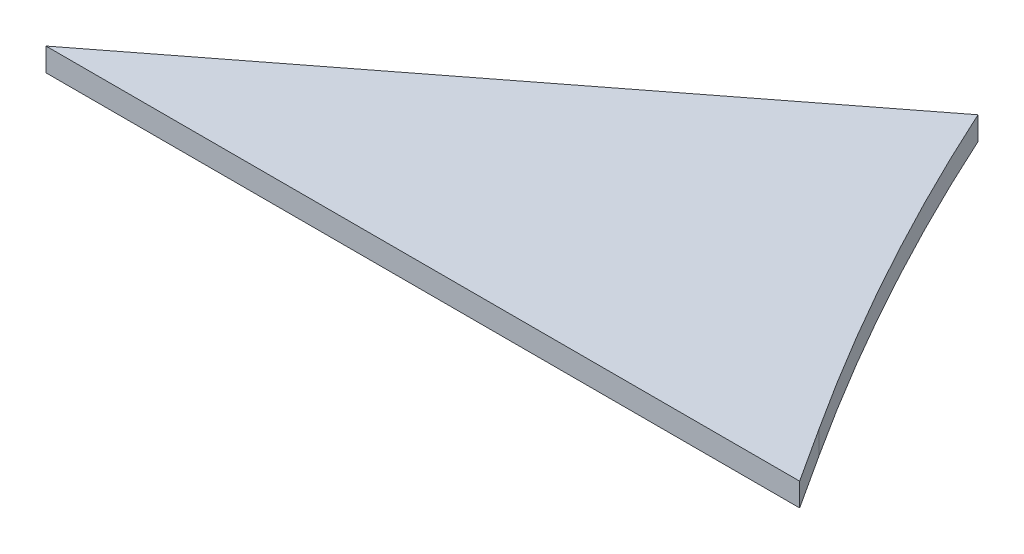
SolidWorks part; units mm, degrees
material "AISI 4130 Steel, normalized at 870C"
ref_plane "Front Plane" through (0, 0, 0) normal (0, 0, 1) x (1, 0, 0)
ref_plane "Top Plane" through (0, 0, 0) normal (0, 1, 0) x (1, 0, 0)
ref_plane "Right Plane" through (0, 0, 0) normal (1, 0, 0) x (0, 0, -1)
sketch "Sketch1" plane through (0, 0, 0) normal (0, 1, 0) x (1, 0, 0)
  line L0 (0, 0) -> (-57.4701, -44.45)
  line L1 (-57.4701, -44.45) -> (24.9464, -44.45)
  line L2 (24.9464, -44.45) -> (21.0374, -38.4076)
  line L3 (0, 0) -> (0, -44.45) construction
  arc A0 (21.0374, -38.4076) -> (0, 0) centre (272.7305, 124.42) cw
  dimension "D2" = 299.7704
  dimension "D3" = 43.7917
  dimension "D1" = 37.72
  dimension "D4" = 57.1
  dimension "D5" = 44.45
base flange "Base-Flange1" sketch "Sketch1" thickness 2.54 reverse thickness direction no parameters "D1"=0.7366
sketch "Bend-Lines1" [suppressed] plane through (0, 0, 0) normal (0, 1, 0) x (1, 0, 0)
sketch "Bounding-Box1" [suppressed] plane through (0, 0, 0) normal (0, 1, 0) x (1, 0, 0)
sheet metal parameters "Sheet-Metal1" thickness 2.54 parameters "D1"=0.7366
flat pattern "Flat-Pattern1" [suppressed]
sketch "Bend-Lines2" plane through (0, 0, 0) normal (0, 1, 0) x (1, 0, 0)
sketch3d "Bounding-Box2" [suppressed]
  line L0 (-247.7842, -124.42, 0) -> (-330.2006, -124.42, 0) construction
  line L1 (-247.7842, -168.87, 0) -> (-330.2006, -168.87, 0) construction
  line L2 (-247.7842, -124.42, 0) -> (-247.7842, -168.87, 0) construction
  line L3 (-330.2006, -124.42, 0) -> (-330.2006, -168.87, 0) construction
